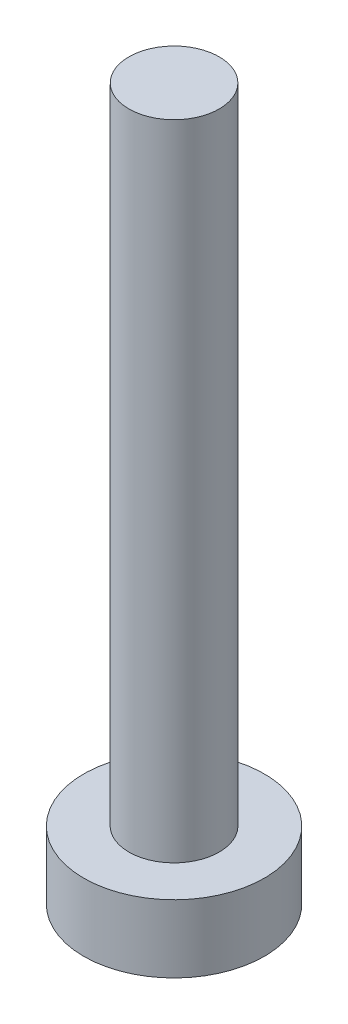
SolidWorks part; units mm, degrees
ref_plane "Plan de face" through (0, 0, 0) normal (0, 0, 1) x (1, 0, 0)
ref_plane "Plan de dessus" through (0, 0, 0) normal (0, 1, 0) x (1, 0, 0)
ref_plane "Plan de droite" through (0, 0, 0) normal (1, 0, 0) x (0, 0, -1)
sketch "Esquisse1" plane through (0, 0, 0) normal (0, 1, 0) x (1, 0, 0)
  circle A0 centre (0, 0) radius 2
  circle A1 centre (0, 0) radius 4
extrude "Boss.-Extru.1" add sketch "Esquisse1" along normal blind 3
extrude "Boss.-Extru.3" add sketch "Esquisse1<4>" along normal blind 31.5 contours A0
sketch "Esquisse1<4>" plane through (0, 0, 0) normal (0, 1, 0) x (1, 0, 0) same geometry as "Esquisse1"
